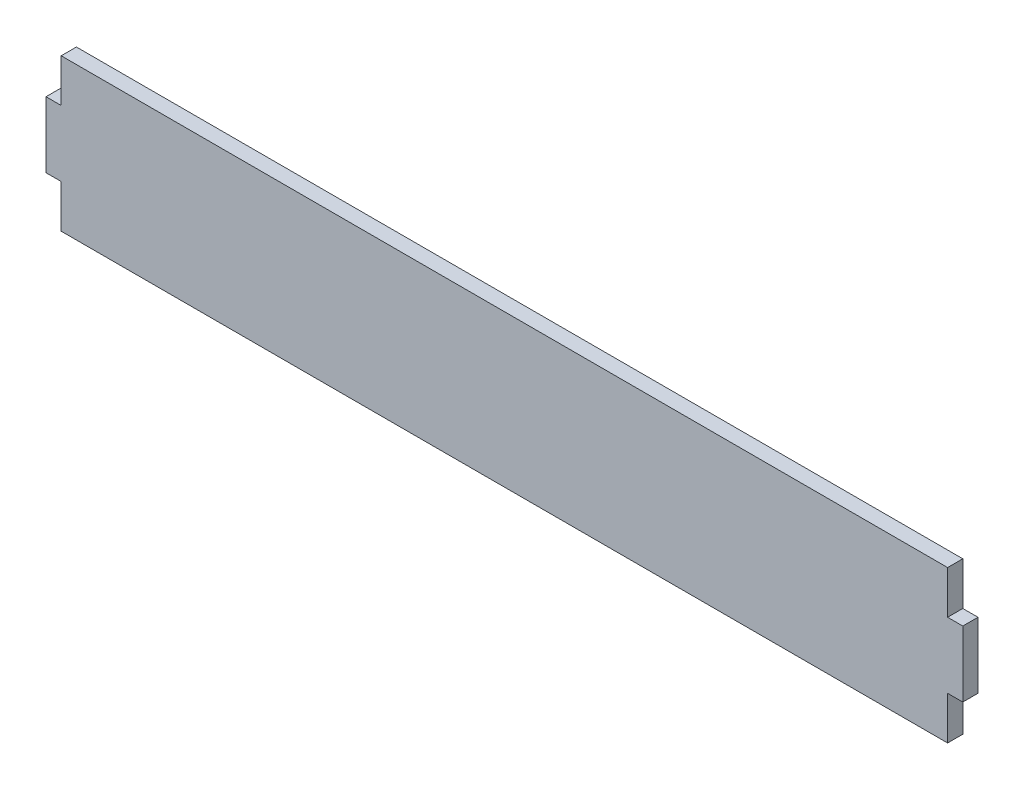
SolidWorks part; units mm, degrees
ref_plane "Front Plane" through (0, 0, 0) normal (0, 0, 1) x (1, 0, 0)
ref_plane "Top Plane" through (0, 0, 0) normal (0, 1, 0) x (1, 0, 0)
ref_plane "Right Plane" through (0, 0, 0) normal (1, 0, 0) x (0, 0, -1)
sketch "Sketch1" plane through (0, 0, 0) normal (0, 0, 1) x (1, 0, 0)
  line L0 (3, 21.5) -> (3, 30)
  line L1 (3, 0) -> (178, 0)
  line L3 (3, 30) -> (178, 30)
  line L5 (0, 21.5) -> (3, 21.5)
  line L6 (0, 21.5) -> (0, 8.5)
  line L7 (0, 8.5) -> (3, 8.5)
  line L10 (0, 0) -> (3, 0) construction
  line L11 (3, 8.5) -> (3, 0)
  line L12 (0, 8.5) -> (0, 0) construction
  line L13 (90.5, 15) -> (90.5, 3.5137) construction
  line L14 (0, 15) -> (181, 15) construction
  line L15 (181, -92.1061) -> (181, 92.2614) construction
  line L16 (178, 8.5) -> (178, 0)
  line L17 (181, 8.5) -> (178, 8.5)
  line L18 (178, 21.5) -> (178, 30)
  line L19 (181, 21.5) -> (178, 21.5)
  line L20 (181, 21.5) -> (181, 8.5)
  dimension "D1" = 30
  dimension "D2" = 13
  dimension "D3" = 3
extrude "Boss-Extrude1" add sketch "Sketch1" along normal blind 3
